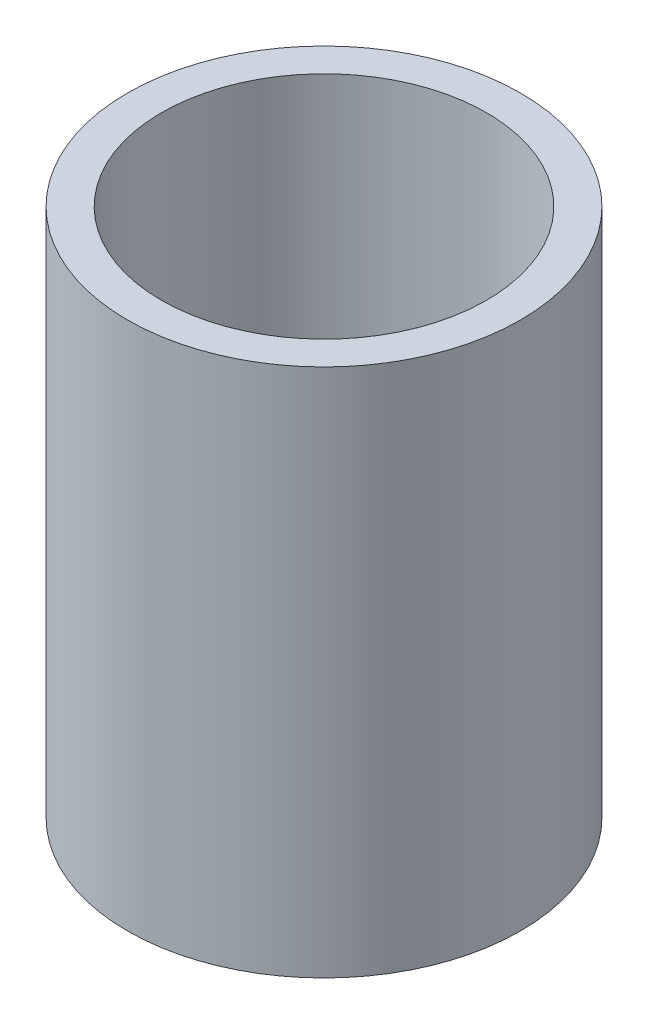
SolidWorks part; units mm, degrees
material "PMMA"
ref_plane "Front Plane" through (0, 0, 0) normal (0, 0, 1) x (1, 0, 0)
ref_plane "Top Plane" through (0, 0, 0) normal (0, 1, 0) x (1, 0, 0)
ref_plane "Right Plane" through (0, 0, 0) normal (1, 0, 0) x (0, 0, -1)
sketch "Sketch1" plane through (0, 0, 0) normal (0, 1, 0) x (1, 0, 0)
  circle A0 centre (0, 0) radius 13
  circle A1 centre (0, 0) radius 10.75
  dimension "D1" = 26
  dimension "D2" = 21.5
extrude "Boss-Extrude1" add sketch "Sketch1" along normal blind 35
